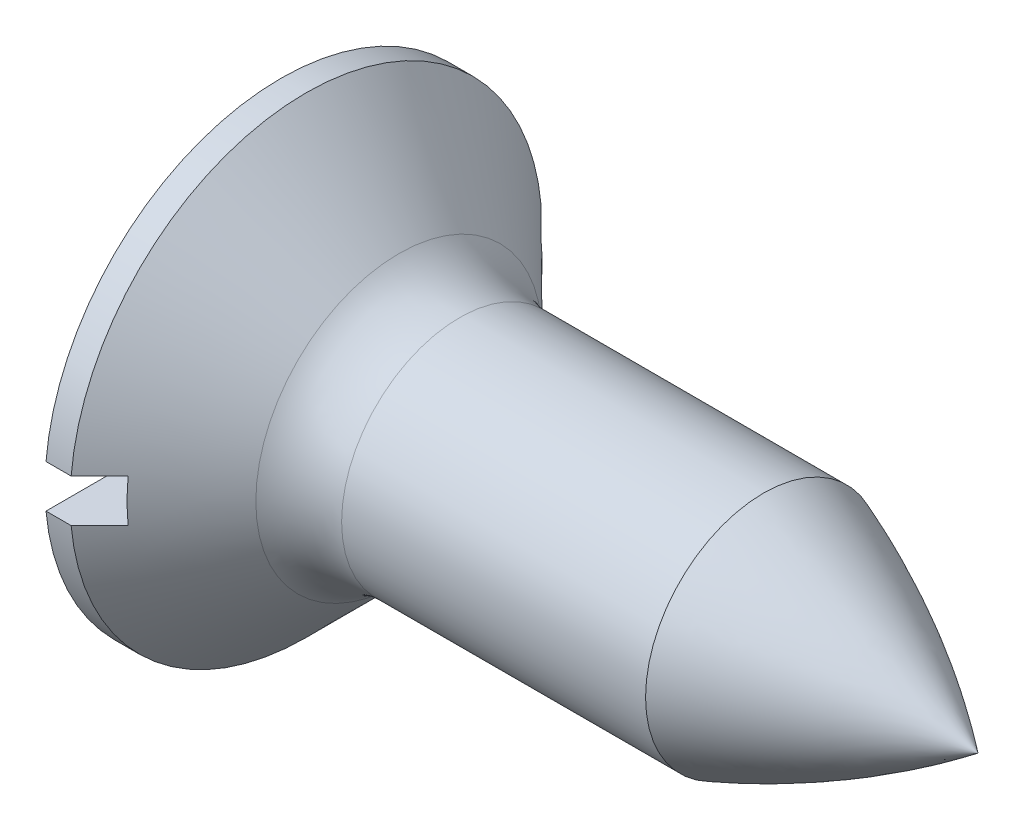
SolidWorks part; units mm, degrees
ref_plane "Front" through (0, 0, 0) normal (0, 0, 1) x (1, 0, 0)
ref_plane "Top" through (0, 0, 0) normal (0, 1, 0) x (1, 0, 0)
ref_plane "Right" through (0, 0, 0) normal (1, 0, 0) x (0, 0, -1)
sketch "Sketch1" plane through (0, 0, 0) normal (0, 0, 1) x (1, 0, 0)
  line L0 (-9.6945, 0) -> (41.8165, 0) construction
  line L1 (6.5, 0) -> (6.5, 1.1)
  line L2 (6.5, 1.1) -> (1.6657, 1.1)
  line L3 (1.1, 1.3343) -> (0.2343, 2.2)
  line L4 (0.2343, 2.2) -> (0, 2.2)
  line L5 (6.5, 0) -> (0, 0)
  line L6 (1.9, 2.8481) -> (1.9, -2.3177) construction
  line L7 (0, 2.2) -> (0, 0)
  arc A0 (1.6657, 1.1) -> (1.1, 1.3343) centre (1.6657, 1.9) cw
  dimension "dk" = 4.4
  dimension "D2" = 45
  dimension "l" = 6.5
  dimension "k" = 1.1
revolve "Base" add sketch "Sketch1" angle 360 about L0
cosmetic thread "ThreadCosmetic1" [suppressed] parameters "D1"=4.6, "D2"=1.2
sketch "Sketch2" plane through (0, 0, 0) normal (0, 0, 1) x (1, 0, 0)
  line L0 (0, 2.2) -> (0, -2.2) construction
  line L1 (0, 0.2) -> (0.5, 0.2)
  line L2 (0, 0.2) -> (0, -0.2)
  line L3 (0, -0.2) -> (0.5, -0.2)
  line L4 (0.5, 0.2) -> (0.5, -0.2)
  line L6 (1.1738, 0) -> (-4.2219, 0) construction
  dimension "n" = 0.4
  dimension "t" = 0.5
extrude "Slot" cut sketch "Sketch2" against normal through all and the other way through all
sketch "Sketch3" plane through (0, 0, 0) normal (0, 0, 1) x (1, 0, 0)
  line L0 (1.3282, 0) -> (-13.6388, 0) construction
  line L1 (1.6657, -1.1) -> (6.5, -1.1) construction
  line L2 (4.9, -1.1) -> (5.7, -1.1)
  line L3 (5.7, -1.1) -> (6.5, -0.9)
  line L6 (4.9, -1.1) -> (4.9, -1.6)
  line L7 (4.9, -1.6) -> (6.5, -1.6)
  line L8 (6.5, -1.6) -> (6.5, -0.9)
  line L9 (6.5, -1.1) -> (6.5, 1.1) construction
  point P15 (5.7, -1.1)
  dimension "D2" = 0.8
  dimension "D4" = 0.5
  dimension "D3" = 0.2
revolve "Cut-Revolve1" [suppressed] cut sketch "Sketch3" angle 360 about L0
sketch "Sketch4" plane through (0, 0, 0) normal (0, 0, 1) x (1, 0, 0)
  line L0 (33.2407, 0) -> (9.9121, 0) construction
  line L2 (6.5, -1.1) -> (6.5, 1.1) construction
  line L3 (6.5, 0) -> (4.5, -1.1) construction
  line L6 (6.5, 0) -> (7, 0)
  line L7 (4.5, -1.1) -> (6.5, -1.1)
  line L8 (7, 0) -> (7, -1.1)
  line L9 (7, -1.1) -> (6.5, -1.1)
  arc A0 (6.5, 0) -> (4.5, -1.1) centre (1.6841, 6.388) cw
  dimension "D1" = 8
  dimension "D3" = 2.2
  dimension "D2" = 0.5
revolve "Cut-Revolve6" cut sketch "Sketch4" angle 360 about L0
sketch "Sketch5" plane through (0, 0, 0) normal (0, 0, 1) x (1, 0, 0)
  line L0 (1.65, 1.6) -> (2.15, 1.6)
  line L1 (2.15, 1.6) -> (2.15, 1.1)
  line L2 (2.15, 1.1) -> (1.9, 0.667)
  line L3 (1.9, 0.667) -> (1.65, 1.1)
  line L4 (1.65, 1.1) -> (1.65, 1.6)
  line L5 (0, 0) -> (8.4251, 0) construction
  dimension "D1" = 2.2
  dimension "D2" = 0.5
  dimension "D3" = 0.8
revolve "Cut-Revolve10" [suppressed] cut sketch "Sketch5" angle 360 about L5
pattern_linear "LPattern10" [suppressed] count 8 spacing 0.6 along (1, 0, 0) of bodies 110
equation "\"D3@Sketch3\" = \"yf@Sketch3\" / 8"
equation "\"D2@ThreadCosmetic1\" = \"st@Sketch1\" - 1"
equation "\"D1@Sketch4\" = \"yc@Sketch4\" * 4"
equation "\"D3@Sketch4\" = \"st@Sketch1\""
equation "\"D2@Sketch3\" = \"yf@Sketch3\" / 2"
equation "\"D1@ThreadCosmetic1\" = \"l@Sketch1\" - \"k@Sketch1\" - \"a@Sketch1\""
equation "\"D1@Sketch5\" = \"st@Sketch1\""
equation "\"D2@Sketch5\" =  ( \"D1@Sketch5\" - \"D2@ThreadCosmetic1\" )  / 2"
equation "\"D3@Sketch5\" = \"a@Sketch1\""
equation "\"D3@LPattern10\" = \"D2@Sketch5\" * 1.2"
equation "\"D1@LPattern10\" = \"D1@ThreadCosmetic1\" / \"D3@LPattern10\""
